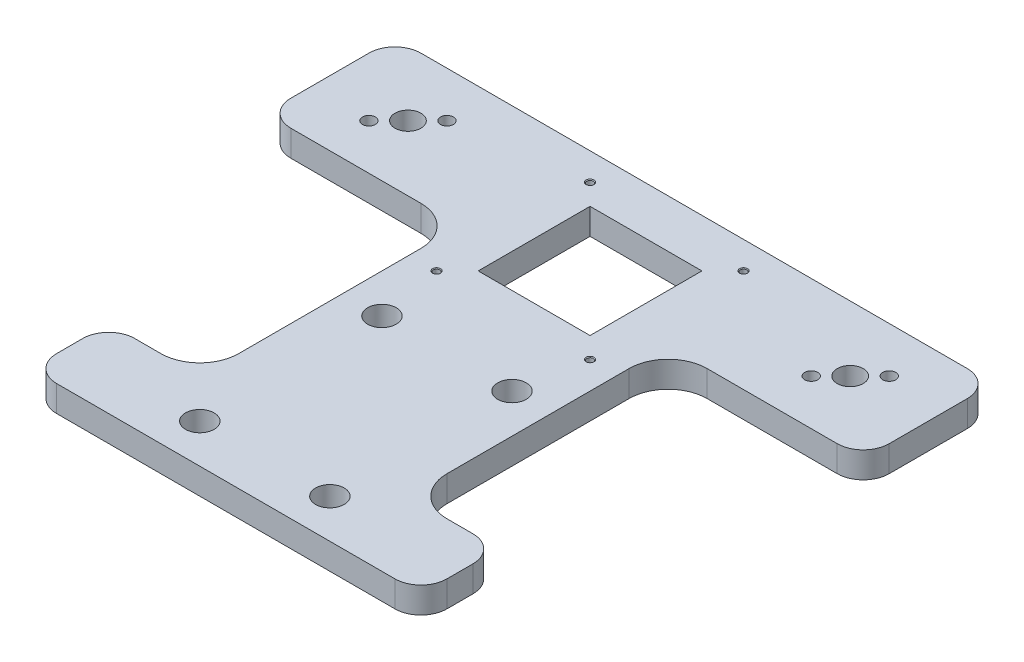
SolidWorks part; units mm, degrees
ref_plane "Vorne" through (0, 0, 0) normal (0, 0, 1) x (1, 0, 0)
ref_plane "Oben" through (0, 0, 0) normal (0, 1, 0) x (1, 0, 0)
ref_plane "Rechts" through (0, 0, 0) normal (1, 0, 0) x (0, 0, -1)
ref_plane "E_Boden" through (0, 1, 0) normal (0, 1, 0) x (1, 0, 0)
sketch "Skizze1" plane through (0, 0, 0) normal (0, 1, 0) x (1, 0, 0)
  line L0 (0, -84.2382) -> (0, 127.1868) construction
  line L1 (-165.4867, 0) -> (188.3198, 0) construction
  line L2 (-105, 90) -> (105, 90)
  line L3 (-115, 80) -> (-115, 50)
  line L8 (-105, 40) -> (-55, 40)
  line L9 (-40, 25) -> (-40, -45)
  line L10 (-55, -60) -> (-65, -60)
  line L11 (-75, -70) -> (-75, -80)
  line L12 (-65, -90) -> (65, -90)
  line L13 (75, -70) -> (75, -80)
  line L14 (55, -60) -> (65, -60)
  line L15 (40, 25) -> (40, -45)
  line L16 (105, 40) -> (55, 40)
  line L17 (115, 80) -> (115, 50)
  arc A0 (40, 25) -> (55, 40) centre (55, 25) cw
  arc A1 (55, -60) -> (40, -45) centre (55, -45) cw
  arc A2 (-40, -45) -> (-55, -60) centre (-55, -45) cw
  arc A3 (-55, 40) -> (-40, 25) centre (-55, 25) cw
  arc A4 (75, -70) -> (65, -60) centre (65, -70) ccw
  arc A5 (75, -80) -> (65, -90) centre (65, -80) cw
  arc A6 (-75, -80) -> (-65, -90) centre (-65, -80) ccw
  arc A7 (-65, -60) -> (-75, -70) centre (-65, -70) ccw
  arc A8 (-115, 50) -> (-105, 40) centre (-105, 50) ccw
  arc A9 (105, 40) -> (115, 50) centre (105, 50) ccw
  arc A10 (115, 80) -> (105, 90) centre (105, 80) ccw
  arc A11 (-105, 90) -> (-115, 80) centre (-105, 80) ccw
  point P15 (0, -90)
  point P16 (0, 90)
  point P22 (40, 40)
  point P25 (40, -60)
  point P28 (-40, -60)
  point P31 (-40, 40)
  point P34 (75, -60)
  point P37 (75, -90)
  point P40 (-75, -90)
  point P43 (-75, -60)
  point P46 (-115, 40)
  point P49 (115, 40)
  point P52 (115, 90)
  point P55 (-115, 90)
  dimension "D7" = 15
  dimension "D8" = 10
  dimension "D1" = 230
  dimension "D2" = 50
  dimension "D3" = 130
  dimension "D4" = 150
  dimension "D5" = 80
  dimension "D6" = 30
extrude "Aufsatz-Linear austragen1" add sketch "Skizze1" along normal blind 10
hole_wizard "Ø10.0 (10) Durchmesser Bohrung1" positions "Skizze6" profile "Skizze7" hole size "Ø10.0" standard "DIN" end condition through all
sketch "Skizze6" plane through (0, 10, 0) normal (0, 1, 0) x (1, 0, 0)
  line L2 (105, 90) -> (-105, 90) construction
  line L3 (0, 90) -> (0, -90) construction
  line L4 (-65, -90) -> (65, -90) construction
  point P0 (-85, 65)
  point P2 (85, 65)
  dimension "D1" = 25
  dimension "D2" = 25
  dimension "D3" = 170
sketch "Skizze7" plane through (-85, 10, -65) normal (1, 0, 0) x (0, 0, 1)
  line L0 (0, 0) -> (0, 10)
  line L1 (0, 10) -> (5, 10)
  line L2 (5, 10) -> (5, 0)
  line L5 (5, 0) -> (0, 0)
  line L11 (0, -6.35) -> (0, 107.95) construction
  dimension "Bohrerdurchmesser" = 10
  dimension "Bohrungstiefe" = 10
sketch "Skizze8" plane through (0, 10, 0) normal (0, 1, 0) x (1, 0, 0)
  line L0 (0, 90) -> (0, -90) construction
  line L1 (-39.1455, 50) -> (35.4895, 50) construction
  line L3 (105, 90) -> (-105, 90) construction
  line L4 (-21.5, 71.5) -> (21.5, 71.5)
  line L5 (-21.5, 71.5) -> (-21.5, 28.5)
  line L6 (-21.5, 28.5) -> (21.5, 28.5)
  line L7 (21.5, 71.5) -> (21.5, 28.5)
  line L8 (-65, -90) -> (65, -90) construction
  dimension "D1" = 43
  dimension "D2" = 43
  dimension "D3" = 40
extrude "Schnitt-Linear austragen2" cut sketch "Skizze8" against normal blind 10
hole_wizard "M3 Gewindebohrung1" positions "Skizze9" profile "Skizze10" tap size "M3" standard "DIN"
sketch "Skizze9" plane through (0, 10, 0) normal (0, 1, 0) x (1, 0, 0)
  line L0 (0, 71.5) -> (0, 28.5) construction
  line L1 (21.5, 71.5) -> (-21.5, 71.5) construction
  line L2 (-21.5, 28.5) -> (21.5, 28.5) construction
  line L4 (-21.5, 50) -> (21.5, 50) construction
  line L5 (-21.5, 71.5) -> (-21.5, 28.5) construction
  line L6 (21.5, 28.5) -> (21.5, 71.5) construction
  point P0 (-29.5, 79.5)
  point P2 (-29.5, 20.5)
  point P4 (29.5, 20.5)
  point P6 (29.5, 79.5)
  dimension "D1" = 8
  dimension "D2" = 8
sketch "Skizze10" plane through (-29.5, 10, -79.5) normal (1, 0, 0) x (0, 0, 1)
  line L0 (0, 0) -> (0, 8.7511)
  line L1 (0, 8.7511) -> (1.25, 8)
  line L2 (1.25, 8) -> (1.25, 0.275)
  line L3 (1.25, 0.275) -> (1.525, 0)
  line L5 (1.525, 0) -> (0, 0)
  line L6 (-1.25, 0.275) -> (-1.525, 0) construction
  line L10 (0, 8.7511) -> (-1.25, 8) construction
  line L11 (0, -6.35) -> (0, 107.95) construction
  dimension "Bohrerdurchmesser" = 2.5
  dimension "Bohrungstiefe" = 8
  dimension "Senkdurchmesser (Oben)" = 3.05
  dimension "Senkwinkel (Oben)" = 90
  dimension "Spitzenwinkel" = 118
cosmetic thread "Bohrungsgewinde1" parameters "D1"=6, "D2"=3
cosmetic thread "Bohrungsgewinde2" parameters "D1"=6, "D2"=3
cosmetic thread "Bohrungsgewinde3" parameters "D1"=6, "D2"=3
cosmetic thread "Bohrungsgewinde4" parameters "D1"=6, "D2"=3
hole_wizard "Ø5.0 (5) Durchmesser Bohrung1" positions "Skizze11" profile "Skizze12" hole size "Ø5.0" standard "DIN" end condition through all
sketch "Skizze11" plane through (0, 0, 0) normal (0, -1, 0) x (-1, 0, 0)
  line L0 (77.5, 72.5) -> (77.5, 45.1453) construction
  line L3 (92.5, 57.5) -> (92.5, 79.091) construction
  line L6 (-92.5, 72.5) -> (-92.5, 57.5) construction
  line L9 (-77.5, 57.5) -> (-77.5, 72.5) construction
  line L12 (-77.5, 57.5) -> (-92.5, 57.5) construction
  line L15 (-77.5, 72.5) -> (-92.5, 72.5) construction
  line L18 (77.5, 72.5) -> (92.5, 72.5) construction
  line L21 (92.5, 57.5) -> (77.5, 57.5) construction
  line L24 (80, 65) -> (71.5087, 65) construction
  line L25 (71.5087, 65) -> (96.6058, 65) construction
  line L28 (85, 60) -> (85, 53.6887) construction
  line L29 (85, 53.6887) -> (85, 75.0654) construction
  line L30 (-90, 65) -> (-74.1442, 65) construction
  line L32 (-85, 70) -> (-85, 55.7381) construction
  circle A0 centre (85, 65) radius 5 construction
  circle A1 centre (-85, 65) radius 5 construction
  point P0 (77.5, 72.5)
  point P2 (92.5, 57.5)
  point P4 (-92.5, 72.5)
  point P6 (-77.5, 57.5)
  point P43 (85, 72.5)
  dimension "D1" = 15
  dimension "D2" = 15
  dimension "D3" = 7.5
  dimension "D4" = 7.5
  dimension "D5" = 15
  dimension "D6" = 15
  dimension "D7" = 7.5
  dimension "D8" = 7.5
sketch "Skizze12" plane through (-77.5, 0, -72.5) normal (1, 0, 0) x (0, 0, -1)
  line L0 (0, 0) -> (0, 10)
  line L1 (0, 10) -> (2.5, 10)
  line L2 (2.5, 10) -> (2.5, 0)
  line L5 (2.5, 0) -> (0, 0)
  line L11 (0, -6.35) -> (0, 107.95) construction
  dimension "Bohrerdurchmesser" = 5
  dimension "Bohrungstiefe" = 10
hole_wizard "Durchgangsloch für M101" positions "Skizze13" profile "Skizze14" hole size "M10" standard "DIN" end condition through all
sketch "Skizze13" plane through (0, 0, 0) normal (0, -1, 0) x (-1, 0, 0)
  line L0 (0, 90) -> (0, -90) construction
  line L1 (-105, 90) -> (105, 90) construction
  line L2 (65, -90) -> (-65, -90) construction
  line L4 (-40, -45) -> (-40, 25) construction
  line L5 (40, 25) -> (40, -45) construction
  point P0 (-25, -5)
  point P2 (-25, -75)
  point P4 (25, -5)
  point P6 (25, -75)
  dimension "D1" = 70
  dimension "D2" = 70
  dimension "D3" = 15
  dimension "D4" = 15
  dimension "D5" = 15
  dimension "D6" = 15
sketch "Skizze14" plane through (25, 0, 5) normal (1, 0, 0) x (0, 0, -1)
  line L0 (0, 0) -> (0, 10)
  line L1 (0, 10) -> (5.5, 10)
  line L2 (5.5, 10) -> (5.5, 0)
  line L5 (5.5, 0) -> (0, 0)
  line L11 (0, -6.35) -> (0, 107.95) construction
  dimension "Bohrerdurchmesser" = 11
  dimension "Bohrungstiefe" = 10
